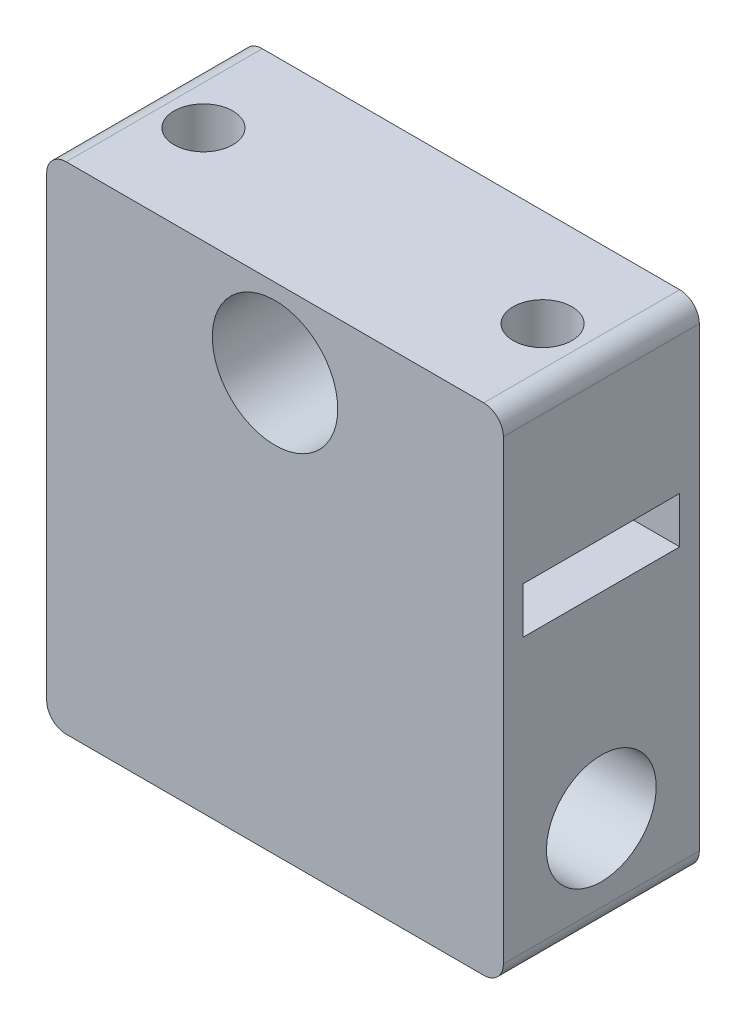
SolidWorks part; units mm, degrees
ref_plane "Front Plane" through (0, 0, 0) normal (0, 0, 1) x (1, 0, 0)
ref_plane "Top Plane" through (0, 0, 0) normal (0, 1, 0) x (1, 0, 0)
ref_plane "Right Plane" through (0, 0, 0) normal (1, 0, 0) x (0, 0, -1)
sketch "Sketch1" plane through (0, 0, 0) normal (0, 0, 1) x (1, 0, 0)
  line L1 (-14.7983, 25.4) -> (14.7983, 25.4)
  line L2 (-14.7983, 25.4) -> (-14.7983, -25.4)
  line L3 (-14.7983, -25.4) -> (14.7983, -25.4)
  line L4 (14.7983, 25.4) -> (14.7983, -25.4)
  line L5 (-14.7983, 25.4) -> (14.7983, -25.4) construction
  line L6 (-14.7983, -25.4) -> (14.7983, 25.4) construction
  circle A0 centre (0, 17.78) radius 4.064
  point P0 (0, 0)
  dimension "D1" = 8.128
  dimension "D2" = 25.4
  dimension "D3" = 7.62
extrude "Boss-Extrude1" add sketch "Sketch1" along normal blind 12.7
sketch "Sketch2" plane through (-14.7983, 0, 0) normal (-1, 0, 0) x (0, 0, 1)
  line L1 (1.27, 12.7) -> (11.43, 12.7)
  line L2 (1.27, 12.7) -> (1.27, 9.7)
  line L3 (1.27, 9.7) -> (11.43, 9.7)
  line L4 (11.43, 12.7) -> (11.43, 9.7)
  line L5 (1.27, 12.7) -> (11.43, 9.7) construction
  line L6 (1.27, 9.7) -> (11.43, 12.7) construction
  line L7 (12.7, 25.4) -> (0, 25.4) construction
  line L8 (12.7, -25.4) -> (0, -25.4) construction
  point P0 (6.35, 11.2)
  point P14 (6.35, -25.4)
  dimension "D1" = 10.16
  dimension "D2" = 3
  dimension "D3" = 12.7
extrude "Cut-Extrude1" cut sketch "Sketch2" against normal blind 30.48
sketch "Sketch3" plane through (-14.7983, 0, 0) normal (-1, 0, 0) x (0, 0, 1)
  line L0 (0, 25.4) -> (0, -25.4) construction
  line L1 (1.27, 9.7) -> (11.43, 9.7) construction
  circle A0 centre (6.35, -3) radius 3.556
  point P4 (6.35, 9.7)
  dimension "D1" = 7.112
  dimension "D2" = 6.35
  dimension "D3" = 12.7
extrude "Cut-Extrude2" cut sketch "Sketch3" against normal blind 45.72
sketch "Sketch4" plane through (0, 25.4, 0) normal (0, 1, 0) x (1, 0, 0)
  line L0 (14.7983, 0) -> (-14.7983, 0) construction
  line L1 (14.7983, -12.7) -> (14.7983, 0) construction
  line L2 (-14.7983, -12.7) -> (-14.7983, 0) construction
  circle A0 centre (10.9883, -6.35) radius 0.762
  circle A1 centre (-10.9883, -6.35) radius 0.762
  dimension "D4" = 1.524
  dimension "D5" = 1.524
  dimension "D1" = 6.35
  dimension "D2" = 3.81
  dimension "D3" = 3.81
extrude "Cut-Extrude3" cut sketch "Sketch4" against normal blind 17.78
sketch "Sketch5" plane through (0, 25.4, 0) normal (0, 1, 0) x (1, 0, 0)
  circle A0 centre (-10.9883, -6.35) radius 1.905
  circle A1 centre (10.9883, -6.35) radius 1.905
  circle A2 centre (-10.9883, -6.35) radius 0.762 construction
  circle A3 centre (10.9883, -6.35) radius 0.762 construction
  dimension "D1" = 3.81
  dimension "D2" = 3.81
extrude "Cut-Extrude4" cut sketch "Sketch5" against normal blind 12.7
sketch "Sketch7" plane through (-14.7983, 0, 0) normal (-1, 0, 0) x (0, 0, 1)
  line L0 (0, 25.4) -> (0, -25.4) construction
  line L1 (0, -14.3495) -> (12.7, -14.3495)
  line L2 (0, -14.3495) -> (0, -25.4)
  line L3 (0, -25.4) -> (12.7, -25.4)
  line L4 (12.7, -14.3495) -> (12.7, -25.4)
extrude "Cut-Extrude5" cut sketch "Sketch7" against normal blind 62.484
sketch "Sketch8" plane through (0, 0, 12.7) normal (0, 0, 1) x (1, 0, 0)
  line L0 (-14.7983, 25.4) -> (-14.7983, -14.3495) construction
  line L1 (14.7983, 25.4) -> (-14.7983, 25.4)
  line L2 (14.7983, 25.4) -> (14.7983, 22.86)
  line L3 (14.7983, 22.86) -> (-14.7983, 22.86)
  line L4 (-14.7983, 25.4) -> (-14.7983, 22.86)
  dimension "D1" = 2.54
extrude "Cut-Extrude6" cut sketch "Sketch8" against normal blind 62.484
sketch "Sketch9" plane through (-14.7983, 0, 0) normal (-1, 0, 0) x (0, 0, 1)
  line L0 (0, 22.86) -> (0, -14.3495) construction
  line L1 (12.7, -14.3495) -> (0, -14.3495)
  line L2 (12.7, -14.3495) -> (12.7, -9.2695)
  line L3 (12.7, -9.2695) -> (0, -9.2695)
  line L4 (0, -14.3495) -> (0, -9.2695)
  dimension "D1" = 5.08
extrude "Cut-Extrude7" cut sketch "Sketch9" against normal blind 62.484
fillet "Fillet1" radius 1.27 4 edges at (-14.7983, 22.86, 6.35) (14.7983, 22.86, 6.35) (14.7983, -9.2695, 6.35) (-14.7983, -9.2695, 6.35)
